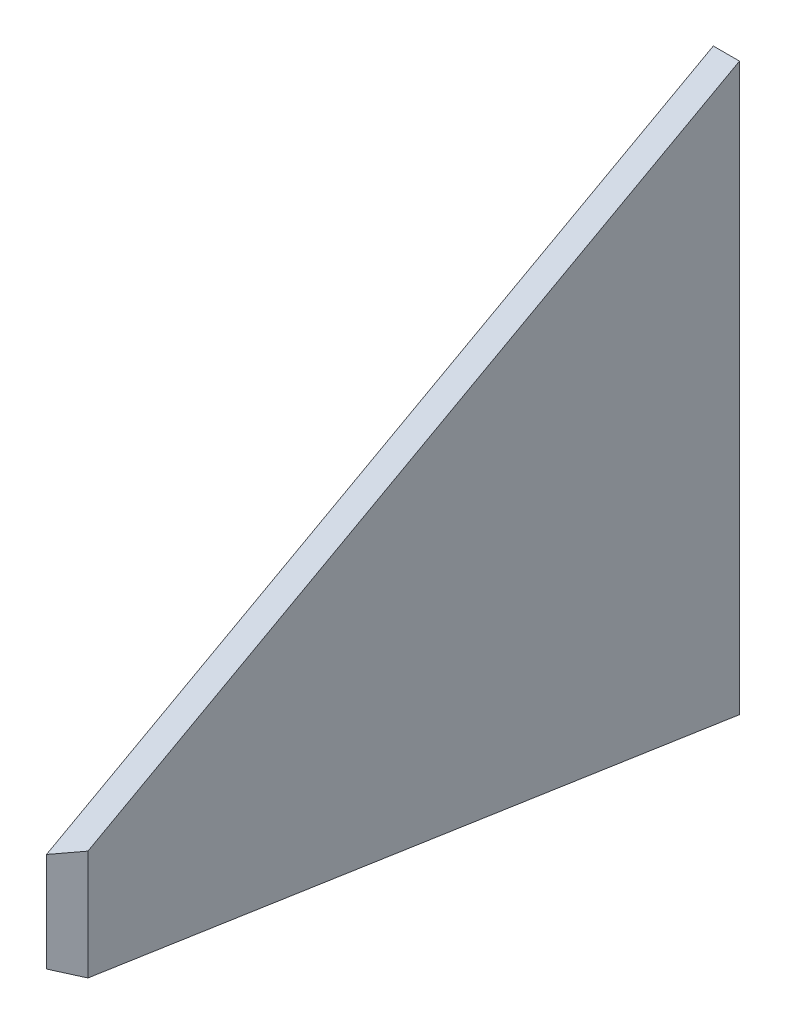
SolidWorks part; units mm, degrees
ref_plane "Front Plane" through (0, 0, 0) normal (0, 0, 1) x (1, 0, 0)
ref_plane "Top Plane" through (0, 0, 0) normal (0, 1, 0) x (1, 0, 0)
ref_plane "Right Plane" through (0, 0, 0) normal (1, 0, 0) x (0, 0, -1)
sketch "Sketch2" plane through (0, 0, 0) normal (0, 1, 0) x (1, 0, 0)
  line L0 (-57.15, 0) -> (224.536, 0)
  line L1 (224.536, 0) -> (-24.3577, -196.7539)
  line L2 (-24.3577, -196.7539) -> (-57.15, 0)
  line L3 (0, 0) -> (0, -152.4) construction
  line L4 (-31.75, -152.4) -> (31.75, -152.4) construction
  point P2 (0, 0)
  dimension "D1" = 281.686
  dimension "D2" = 57.15
  dimension "D3" = 63.5
  dimension "D4" = 152.4
extrude "Boss-Extrude1" add sketch "Sketch2" along normal blind 152.4
ref_plane "Plane1" through (-63.5, 0, 0) normal (1, 0, 0) x (0, 0, -1)
sketch "Sketch3" plane through (-63.5, 0, 0) normal (1, 0, 0) x (0, 0, -1)
  line L0 (0, 76.2) -> (-152.4, 76.2) construction
  line L1 (0, 152.4) -> (0, 0) construction
  line L2 (-152.4, 44.45) -> (-152.4, 107.95) construction
  line L3 (0, 152.4) -> (-152.4, 107.95)
  line L4 (0, 0) -> (-152.4, 44.45)
  line L5 (-152.4, 107.95) -> (-261.2571, 76.2)
  line L6 (-152.4, 44.45) -> (-261.2571, 76.2)
  line L7 (0, 152.4) -> (0, 0)
  point P7 (-152.4, 76.2)
  dimension "D1" = 152.4
  dimension "D2" = 63.5
extrude "Cut-Extrude2" cut sketch "Sketch3" along normal through all flip side to cut
shell "Shell1" thickness 6.35 removed face at (83.693, 76.2, 0)
sketch "Sketch4" plane through (-63.5, 0, 0) normal (1, 0, 0) x (0, 0, -1)
  line L1 (0, 152.4) -> (0, 145.7854)
  line L2 (0, 145.7854) -> (-196.7539, 88.3989)
  line L4 (-196.7539, 64.0011) -> (0, 6.6146)
  line L5 (0, 152.4) -> (-196.7539, 95.0134)
  line L7 (-196.7539, 57.3866) -> (0, 0)
  line L8 (-196.7539, 95.0134) -> (-196.7539, 57.3866) construction
  line L9 (-196.7539, 95.0134) -> (-196.7539, 88.3989)
  line L10 (-196.7539, 64.0011) -> (-196.7539, 57.3866)
  line L11 (0, 152.4) -> (0, 0) construction
  line L12 (0, 0) -> (0, 6.6146)
extrude "Cut-Extrude3" cut sketch "Sketch4" along normal through all
ref_plane "Plane2" through (0, 149.86, 0) normal (0, 1, 0) x (1, 0, 0)
sketch "Sketch5" plane through (0, 149.86, 0) normal (0, 1, 0) x (1, 0, 0)
  line L0 (-19.8615, -185.1052) -> (-18.6695, -192.2573)
  line L1 (-24.3577, -196.7539) -> (224.536, 0) construction
  line L2 (-19.8615, -185.1052) -> (-50.7124, 0) construction
  line L3 (-18.6695, -192.2573) -> (344.3171, -192.2573)
  line L4 (344.3171, -192.2573) -> (317.8797, 72.8643)
  line L5 (317.8797, 72.8643) -> (-35.1367, 43.3166)
  line L6 (-35.1367, 43.3166) -> (-19.8615, -185.1052)
extrude "Cut-Extrude4" cut sketch "Sketch5" against normal through all
